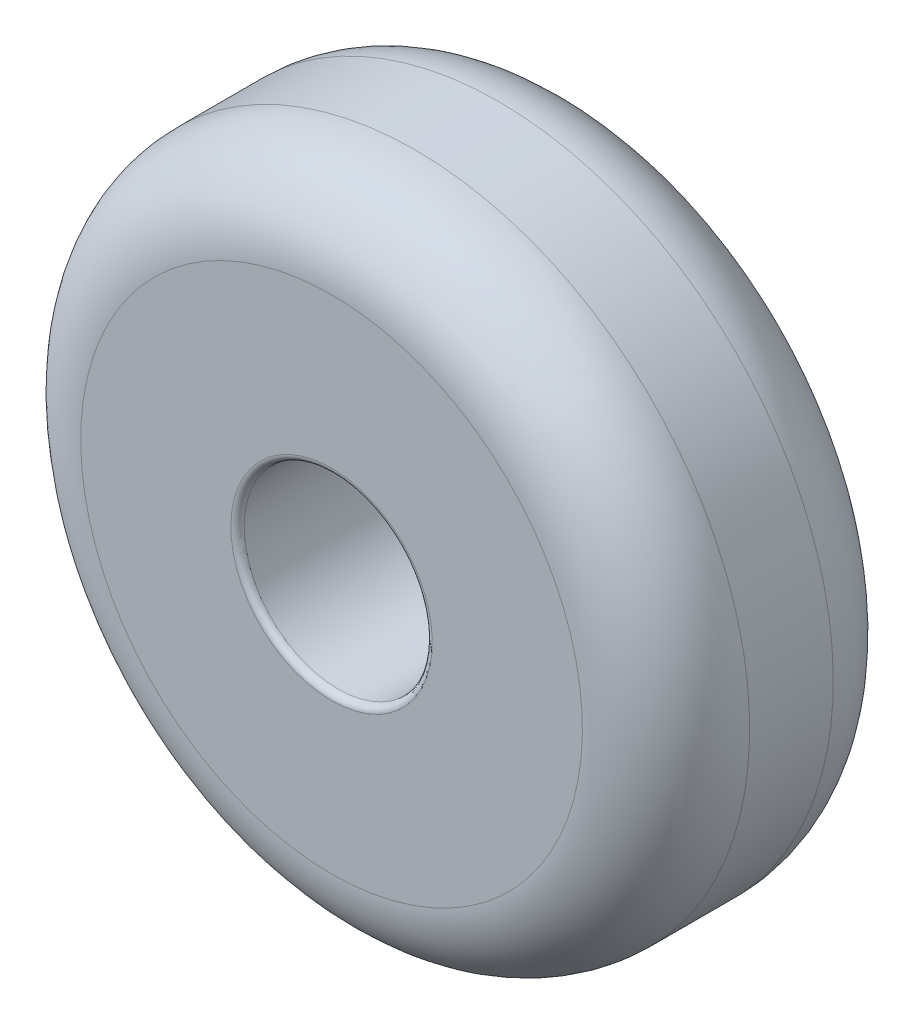
SolidWorks part; units mm, degrees
material "Teak"
ref_plane "Front Plane" through (0, 0, 0) normal (0, 0, 1) x (1, 0, 0)
ref_plane "Top Plane" through (0, 0, 0) normal (0, 1, 0) x (1, 0, 0)
ref_plane "Right Plane" through (0, 0, 0) normal (1, 0, 0) x (0, 0, -1)
ref_axis "X-Axis" through (-13.97, 0, 0) along (1, 0, 0)
ref_axis "Y-Axis" through (0, 13.97, 0) along (0, -1, 0)
ref_axis "Z-Axis" through (0, 0, -5.2388) along (0, 0, 1)
sketch "Sketch1" plane through (0, 0, 0) normal (1, 0, 0) x (0, 0, -1)
  line L0 (-4.7625, 3.5719) -> (4.7625, 3.5719)
  line L1 (4.7625, 3.5719) -> (4.7625, 12.7)
  line L2 (-4.7625, 12.7) -> (-4.7625, 3.5719)
  line L3 (0, 0) -> (-4.7625, 0) construction
  line L4 (-4.7625, 12.7) -> (4.7625, 12.7)
  line L5 (0, 0) -> (0, 3.5719) construction
  dimension "D1" = 7.1437
  dimension "D2" = 25.4
  dimension "D3" = 9.525
revolve "Revolve1" add sketch "Sketch1" angle 360 about L3
fillet "Fillet1" radius 3.175 2 edges at (0, 12.7, -4.7625) (0, 12.7, 4.7625)
fillet "Fillet2" radius 0.254 2 edges at (0, 3.5719, -4.7625) (0, 3.5719, 4.7625)
